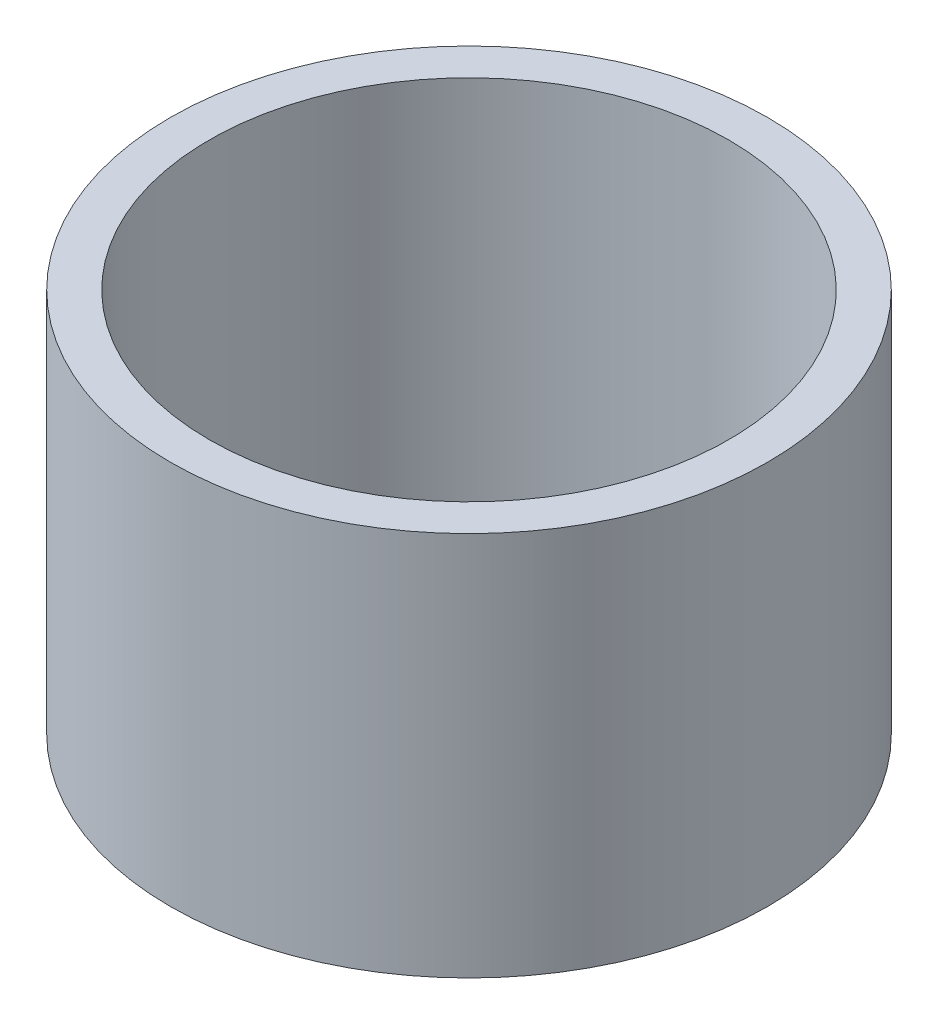
SolidWorks part; units mm, degrees
ref_plane "Front Plane" through (0, 0, 0) normal (0, 0, 1) x (1, 0, 0)
ref_plane "Top Plane" through (0, 0, 0) normal (0, 1, 0) x (1, 0, 0)
ref_plane "Right Plane" through (0, 0, 0) normal (1, 0, 0) x (0, 0, -1)
sketch "Sketch1" plane through (0, 0, 0) normal (0, 1, 0) x (1, 0, 0)
  circle A0 centre (0, 0) radius 37.946
  dimension "D1" = 75.892
extrude "Boss-Extrude1" add sketch "Sketch1" along normal blind 48.9
sketch "Sketch2" plane through (0, 48.9, 0) normal (0, 1, 0) x (1, 0, 0)
  circle A0 centre (0, 0) radius 33
  dimension "D1" = 66
extrude "Cut-Extrude1" cut sketch "Sketch2" against normal blind 46.9
sketch "Sketch3" plane through (0, 0, 0) normal (0, -1, 0) x (1, 0, 0)
  circle A0 centre (0, 0) radius 15
  dimension "D1" = 30
extrude "Boss-Extrude2" add sketch "Sketch3" along normal blind 10
